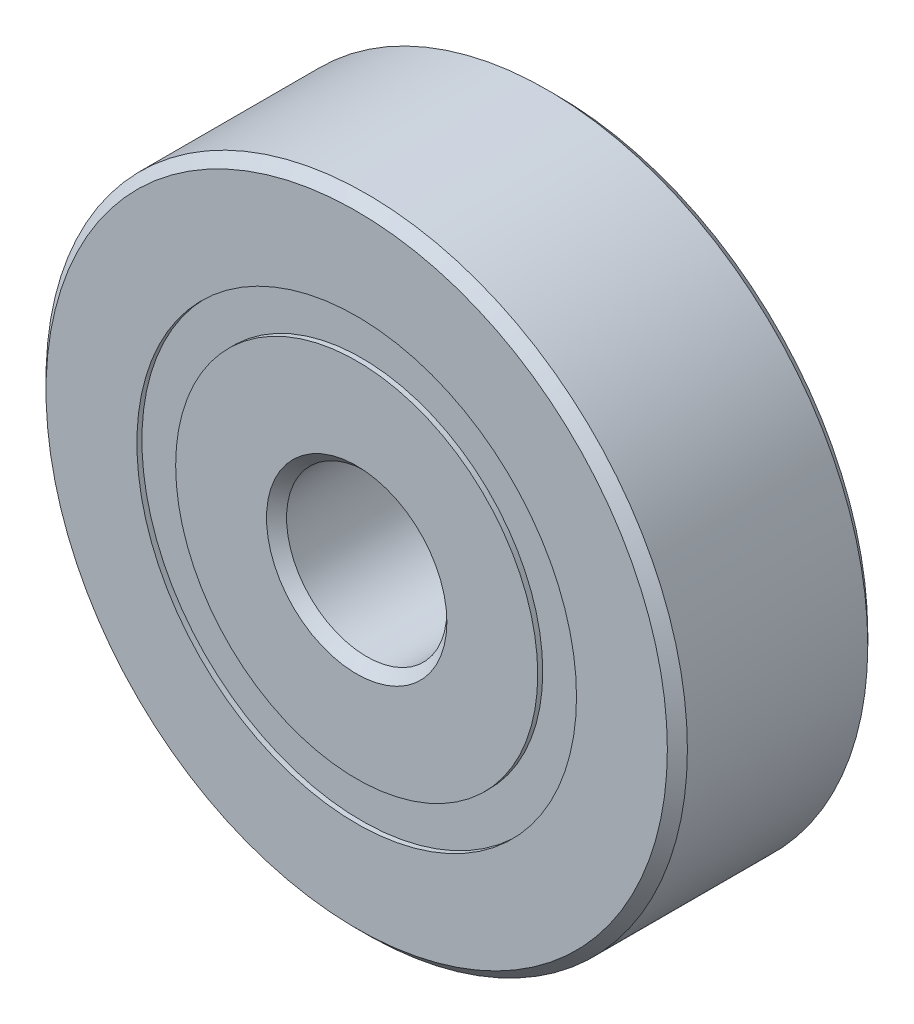
SolidWorks part; units mm, degrees
ref_plane "Front Plane" through (0, 0, 0) normal (0, 0, 1) x (1, 0, 0)
ref_plane "Top Plane" through (0, 0, 0) normal (0, 1, 0) x (1, 0, 0)
ref_plane "Right Plane" through (0, 0, 0) normal (1, 0, 0) x (0, 0, -1)
sketch "Sketch1" plane through (0, 0, 0) normal (1, 0, 0) x (0, 0, -1)
  line L0 (-2.5, 0) -> (2.5, 0) construction
  line L1 (0, 8) -> (0, -8) construction
  line L2 (2.25, 8) -> (-2.25, 8)
  line L3 (-2.25, 8) -> (-2.5, 7.75)
  line L4 (-2.5, 7.75) -> (-2.5, 5.4835)
  line L5 (-2.5, 5.4835) -> (-1.1111, 5.4835)
  line L6 (2.5, 5.4835) -> (1.1111, 5.4835)
  line L7 (2.5, 7.75) -> (2.5, 5.4835)
  line L8 (2.25, 8) -> (2.5, 7.75)
  line L9 (0, 8) -> (0, 5) construction
  line L10 (0, 5) -> (0, 2) construction
  arc A0 (-1.1111, 5.4835) -> (1.1111, 5.4835) centre (0, 5) cw
  point P14 (0, 2)
  dimension "Width" = 5
  dimension "OD" = 16
  dimension "D1" = 45
  dimension "D2" = 0.25
  dimension "Shaft Dia" = 4
  dimension "D3" = 2.2222
  dimension "D4" = 0.4835
revolve "Revolve1" add sketch "Sketch1" angle 360 about L0
sketch "Sketch3" plane through (0, 0, 0) normal (1, 0, 0) x (0, 0, -1)
  line L0 (-2.5, 4.5165) -> (-1.1111, 4.5165)
  line L1 (0, 8) -> (0, -8) construction
  line L2 (-2.5, 7.75) -> (-2.5, 5.4835) construction
  line L3 (-2.5, 4.5165) -> (-2.5, 2.25)
  line L4 (-2.25, 8) -> (-2.5, 7.75) construction
  line L5 (-2.5, 2.25) -> (-2.25, 2)
  line L6 (-2.25, 2) -> (2.25, 2)
  line L7 (2.25, 8) -> (2.25, -8) construction
  line L8 (2.25, 2) -> (2.5, 2.25)
  line L9 (2.5, -7.75) -> (2.5, 7.75) construction
  line L10 (2.5, 2.25) -> (2.5, 4.5165)
  line L11 (2.5, 4.5165) -> (1.1111, 4.5165)
  line L13 (2.25, 8) -> (2.5, 7.75) construction
  arc A0 (1.1111, 5.4835) -> (-1.1111, 5.4835) centre (0, 5) ccw construction
  arc A1 (1.1111, 4.5165) -> (-1.1111, 4.5165) centre (0, 5) cw
revolve "Revolve3" add sketch "Sketch3" angle 360 about L0
sketch "Sketch4" plane through (0, 0, 0) normal (1, 0, 0) x (0, 0, -1)
  line L0 (-1.2118, 5) -> (1.2118, 5)
  arc A2 (-1.2118, 5) -> (1.2118, 5) centre (0, 5) cw
  arc A3 (1.1111, 5.4835) -> (-1.1111, 5.4835) centre (0, 5) ccw construction
revolve "Revolve4" add sketch "Sketch4" angle 360 about L0
ref_axis "Axis1" through (0, 0, -2.5) along (0, 0, 1)
pattern_circular "CirPattern1" count 12 every 30 about axis through (0, 0, -2.5) along (0, 0, 1) of bodies 104
sketch "Sketch5" plane through (0, 0, 0) normal (1, 0, 0) x (0, 0, -1)
  line L0 (-2.5, 5.4835) -> (-1.1111, 5.4835) construction
  line L1 (-2.375, 5.4835) -> (-1.2118, 5.4835)
  line L2 (-2.375, 5.4835) -> (-2.375, 4.5165)
  line L3 (-2.375, 4.5165) -> (-1.2118, 4.5165)
  line L4 (-1.2118, 5.4835) -> (-1.2118, 4.5165)
  line L5 (-2.5, 4.5165) -> (-1.1111, 4.5165) construction
  line L6 (2.5, 5.4835) -> (1.1111, 5.4835) construction
  line L7 (2.375, 5.4835) -> (1.2118, 5.4835)
  line L8 (2.375, 5.4835) -> (2.375, 4.5165)
  line L9 (2.375, 4.5165) -> (1.2118, 4.5165)
  line L10 (1.2118, 5.4835) -> (1.2118, 4.5165)
  line L11 (2.5, 4.5165) -> (1.1111, 4.5165) construction
  line L12 (-2.25, 8) -> (-2.5, 7.75) construction
  point P18 (-2.375, 7.875)
revolve "Revolve5" add sketch "Sketch5" angle 360 about L0
equation "\"D2@Sketch1\" = \"Width@Sketch1\"*.05"
equation "\"D3@Sketch1\" = \"Width@Sketch1\"/2.25"
equation "\"D4@Sketch1\" = (((\"OD@Sketch1\"-\"Width@Sketch1\")/2)/3.25)/3.5"
equation "\"D2@CirPattern1\" = 360/\"Balls@CirPattern1\""
